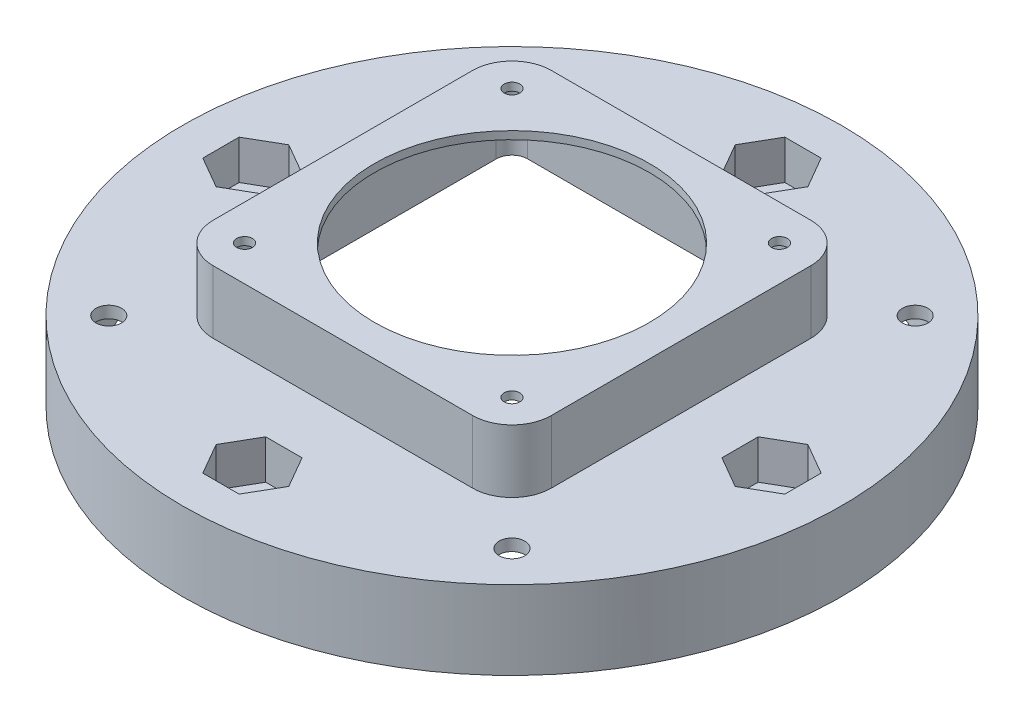
SolidWorks part; units mm, degrees
ref_plane "Front" through (0, 0, 0) normal (0, 0, 1) x (1, 0, 0)
ref_plane "Top" through (0, 0, 0) normal (0, 1, 0) x (1, 0, 0)
ref_plane "Right" through (0, 0, 0) normal (1, 0, 0) x (0, 0, -1)
sketch "Sketch1" plane through (0, 0, 0) normal (0, 1, 0) x (1, 0, 0)
  circle A0 centre (0, 0) radius 41.9
  dimension "D1" = 83.8
extrude "Top-Part" add sketch "Sketch1" along normal blind 15
sketch "Sketch2" plane through (0, 15, 0) normal (0, 1, 0) x (1, 0, 0)
  circle A0 centre (0, 0) radius 30
  dimension "D1" = 60
extrude "Cut-Extrude1" cut sketch "Sketch2" against normal blind 20
fillet "Fillet1" radius 1.5 1 edges at (0, 15, 41.9)
chamfer "Chamfer1" distance 2 angle 45 1 edges at (0, 15, 30)
sketch "Sketch8" plane through (0, 15, 0) normal (0, 1, 0) x (1, 0, 0)
  line L0 (0, 0) -> (0, 52.711) construction
  line L1 (25.0832, 22.5168) -> (28.0563, 23.5989)
  line L8 (0, 0) -> (-43.3951, 43.3951) construction
  line L9 (-25.6326, 25.6326) -> (-25.6326, 34.5059) construction
  line L10 (-22.5168, 25.0832) -> (-23.5989, 28.0563)
  line L11 (-23.5989, 28.0563) -> (-26.7147, 28.6057)
  line L12 (-26.7147, 28.6057) -> (-28.7485, 26.182)
  line L13 (-28.7485, 26.182) -> (-27.6663, 23.2089)
  line L14 (-27.6663, 23.2089) -> (-24.5505, 22.6595)
  line L15 (-24.5505, 22.6595) -> (-22.5168, 25.0832)
  line L16 (28.0563, 23.5989) -> (28.6057, 26.7147)
  line L17 (28.6057, 26.7147) -> (26.182, 28.7485)
  line L18 (26.182, 28.7485) -> (23.2089, 27.6663)
  line L19 (23.2089, 27.6663) -> (22.6595, 24.5505)
  line L20 (22.6595, 24.5505) -> (25.0832, 22.5168)
  line L21 (0, 0) -> (43.3951, 43.3951) construction
  line L23 (22.5168, -25.0832) -> (23.5989, -28.0563)
  line L24 (23.5989, -28.0563) -> (26.7147, -28.6057)
  line L25 (26.7147, -28.6057) -> (28.7485, -26.182)
  line L26 (28.7485, -26.182) -> (27.6663, -23.2089)
  line L27 (27.6663, -23.2089) -> (24.5505, -22.6595)
  line L28 (24.5505, -22.6595) -> (22.5168, -25.0832)
  line L29 (0, 0) -> (43.3951, -43.3951) construction
  line L31 (-25.0832, -22.5168) -> (-28.0563, -23.5989)
  line L32 (-28.0563, -23.5989) -> (-28.6057, -26.7147)
  line L33 (-28.6057, -26.7147) -> (-26.182, -28.7485)
  line L34 (-26.182, -28.7485) -> (-23.2089, -27.6663)
  line L35 (-23.2089, -27.6663) -> (-22.6595, -24.5505)
  line L36 (-22.6595, -24.5505) -> (-25.0832, -22.5168)
  line L37 (0, 0) -> (-43.3951, -43.3951) construction
  line L39 (-25.6326, 25.6326) -> (-27.9138, 12.6954) construction
  circle A0 centre (0, 0) radius 36.25 construction
  circle A1 centre (25.6326, 25.6326) radius 2.74 construction
  circle A2 centre (-25.6326, 25.6326) radius 2.74 construction
  circle A3 centre (25.6326, -25.6326) radius 2.74 construction
  circle A4 centre (-25.6326, -25.6326) radius 2.74 construction
  circle A5 centre (-25.6326, 25.6326) radius 1.625
  circle A6 centre (25.6326, 25.6326) radius 1.625
  circle A7 centre (25.6326, -25.6326) radius 1.625
  circle A8 centre (-25.6326, -25.6326) radius 1.625
  point P8 (25.6326, 25.6326)
  point P10 (28.331, 25.1568)
  point P18 (-25.6326, 25.6326)
  point P20 (-25.1568, 28.331)
  point P36 (25.6326, -25.6326)
  point P38 (25.1568, -28.331)
  point P50 (-25.6326, -25.6326)
  point P52 (-28.331, -25.1568)
  point P63 (0, 0)
  point P69 (-27.8231, 23.2366)
  dimension "D1" = 72.5
  dimension "D5" = 3.25
  dimension "D2" = 4
  dimension "D3" = 45
  dimension "D4" = 10
  dimension "D6" = 5.75
extrude "Cut-Extrude8" cut sketch "Sketch8<7>" against normal blind 3
sketch "Sketch8<7>" plane through (0, 15, 0) normal (0, 1, 0) x (1, 0, 0) same geometry as "Sketch8"
extrude "Cut-Extrude7" cut sketch "Sketch8" against normal through all contours A5 | A6 | A7 | A8
sketch "Sketch13" plane through (0, 0, 0) normal (0, -1, 0) x (1, 0, 0)
  line L0 (0, 0) -> (0, 66.0162) construction
  line L1 (-10, 35.5191) -> (-10, 40.6892)
  line L2 (10, 35.5191) -> (10, 40.6892)
  line L3 (-10, 40.6892) -> (10, 35.5191) construction
  line L4 (10, 40.6892) -> (-10, 35.5191) construction
  circle A0 centre (0, 0) radius 41.9 construction
  arc A1 (10, 40.6892) -> (-10, 40.6892) centre (0, 0) ccw
  arc A2 (10, 35.5191) -> (-10, 35.5191) centre (0, 0) ccw
  point P6 (0, 38.1042)
  point P10 (0, 36.9)
  point P12 (0, 41.9)
  dimension "D1" = 10
  dimension "D3" = 5
extrude "Cut-Extrude11" cut sketch "Sketch13" against normal through all
ref_plane "Plane2" through (0, 0, 41.9) normal (0, 0, 1) x (1, 0, 0)
ref_plane "Plane3" through (0, 0, 32.4) normal (0, 0, 1) x (1, 0, 0)
sketch "Sketch15" plane through (0, 0, 32.4) normal (0, 0, 1) x (1, 0, 0)
  line L0 (0, -23.0183) -> (0, 33.1182) construction
  circle A1 centre (0, 7.5) radius 1.625
  point P11 (0, 7.5)
  dimension "D3" = 3.25
  dimension "D1" = 7.5
extrude "Cut-Extrude14" cut sketch "Sketch15" against normal blind 10 and the other way blind 10
sketch "Sketch16" plane through (0, 0, 32.4) normal (0, 0, 1) x (1, 0, 0)
  line L0 (0, 0) -> (0, 26.985) construction
  line L2 (3.3775, 7.5) -> (1.6887, 10.425)
  line L3 (1.6887, 10.425) -> (-1.6887, 10.425)
  line L4 (-1.6887, 10.425) -> (-3.3775, 7.5)
  line L5 (-3.3775, 7.5) -> (-1.6887, 4.575)
  line L6 (-1.6887, 4.575) -> (1.6887, 4.575)
  line L7 (1.6887, 4.575) -> (3.3775, 7.5)
  circle A0 centre (0, 7.5) radius 2.925 construction
  point P4 (0, 4.575)
  point P13 (0, 10.425)
  dimension "D1" = 5.85
  dimension "D2" = 7.5
extrude "Cut-Extrude15" cut sketch "Sketch16" against normal blind 10
pattern_circular "CirPattern1" count 4 over 360 about axis through (0, 0, 0) along (0, 1, 0) of "Cut-Extrude14"
pattern_circular "CirPattern2" count 4 every 90 about axis through (0, 0, 0) along (0, 1, 0) of "Cut-Extrude15"
sketch "Sketch3" plane through (0, 0, 0) normal (0, -1, 0) x (1, 0, 0)
  circle A0 centre (0, 0) radius 41.9
  dimension "D1" = 83.8
extrude "Bottom-Part" add sketch "Sketch3" along normal blind 20 separate body
ref_plane "Plane1" through (0, -1.5, 0) normal (0, 1, 0) x (1, 0, 0)
sketch "Sketch6" plane through (0, -1.5, 0) normal (0, 1, 0) x (1, 0, 0)
  line L0 (0, 0) -> (-97.4577, 0) construction
  line L5 (-37.9, 0) -> (-41.9, 0) construction
  circle A0 centre (0, 0) radius 37.9
  circle A1 centre (0, 0) radius 41.9 construction
  circle A2 centre (0, 0) radius 41.9 construction
  point P6 (-37.9, 0)
  point P9 (-41.9, 0)
  dimension "D1" = 4
extrude "Cut-Extrude3" cut sketch "Sketch6" against normal through all
sketch "ｽｹｯﾁ1" plane through (0, 0, 0) normal (0, 1, 0) x (1, 0, 0)
  line L3 (21.5, -21.5) -> (-21.5, -21.5)
  line L4 (21.5, -21.5) -> (21.5, 21.5)
  line L5 (21.5, 21.5) -> (-21.5, 21.5)
  line L6 (-21.5, -21.5) -> (-21.5, 21.5)
  line L7 (21.5, -21.5) -> (-21.5, 21.5) construction
  line L8 (21.5, 21.5) -> (-21.5, -21.5) construction
  point P2 (0, 0)
  dimension "D1" = 43
extrude "ﾎﾞｽ - 押し出し1" add sketch "ｽｹｯﾁ1" along normal blind 8
fillet "ﾌｨﾚｯﾄ1" radius 5 4 edges at (21.5, 4, -21.5) (-21.5, 4, -21.5) (-21.5, 4, 21.5) (21.5, 4, 21.5)
sketch "Sketch7" plane through (0, -1.5, 0) normal (0, 1, 0) x (1, 0, 0)
  circle A0 centre (0, 0) radius 17.5
  circle A1 centre (17, -17) radius 1
  circle A2 centre (-17, -17) radius 1
  circle A3 centre (-17, 17) radius 1
  circle A4 centre (17, 17) radius 1
  dimension "D1" = 35
  dimension "D2" = 2
extrude "Cut-Extrude4" cut sketch "Sketch7" against normal through all and the other way through all
sketch "Sketch12" plane through (0, -1.5, 0) normal (0, -1, 0) x (1, 0, 0)
  line L1 (19.75, -19.75) -> (-19.75, -19.75)
  line L2 (19.75, -19.75) -> (19.75, 19.75)
  line L3 (19.75, 19.75) -> (-19.75, 19.75)
  line L4 (-19.75, -19.75) -> (-19.75, 19.75)
  line L5 (19.75, -19.75) -> (-19.75, 19.75) construction
  line L6 (19.75, 19.75) -> (-19.75, -19.75) construction
  point P0 (0, 0)
  dimension "D1" = 39.5
extrude "Cut-Extrude10" cut sketch "Sketch12" against normal blind 8.5
fillet "Fillet3" radius 2 4 edges at (-19.75, 2.75, -19.75) (-19.75, 2.75, 19.75) (19.75, 2.75, -19.75) (19.75, 2.75, 19.75)
sketch "Sketch17" plane through (0, -1.5, 0) normal (0, -1, 0) x (1, 0, 0)
  circle A0 centre (25.6326, -25.6326) radius 1.625 construction
  circle A1 centre (-25.6326, -25.6326) radius 1.625 construction
  circle A2 centre (25.6326, 25.6326) radius 1.625 construction
  circle A3 centre (-25.6326, 25.6326) radius 1.625 construction
  circle A4 centre (25.6326, -25.6326) radius 1.625
  circle A5 centre (-25.6326, -25.6326) radius 1.625
  circle A6 centre (25.6326, 25.6326) radius 1.625
  circle A7 centre (-25.6326, 25.6326) radius 1.625
extrude "Cut-Extrude16" cut sketch "Sketch17" against normal through all
sketch "Sketch18" plane through (0, -1.5, 0) normal (0, -1, 0) x (1, 0, 0)
  circle A0 centre (-25.6326, 25.6326) radius 3
  circle A1 centre (25.6326, 25.6326) radius 3
  circle A2 centre (25.6326, -25.6326) radius 3
  circle A3 centre (-25.6326, -25.6326) radius 3
  dimension "D1" = 6
extrude "Cut-Extrude17" cut sketch "Sketch18" along normal through all
sketch "Sketch19" plane through (0, -1.5, 0) normal (0, -1, 0) x (1, 0, 0)
  line L0 (-6, 33) -> (-6, 37.4221)
  line L1 (6, 33) -> (6, 37.4221)
  line L2 (33, 6) -> (37.4221, 6)
  line L3 (33, -6) -> (37.4221, -6)
  line L4 (6, -33) -> (6, -37.4221)
  line L5 (-6, -33) -> (-6, -37.4221)
  line L6 (-33, -6) -> (-37.4221, -6)
  line L7 (-33, 6) -> (-37.4221, 6)
  arc A0 (-6, 33) -> (6, 33) centre (0, 33) ccw
  arc A1 (24.9276, 28.5486) -> (-24.9276, 28.5486) centre (0, 0) ccw construction
  arc A2 (24.9276, 28.5486) -> (-24.9276, 28.5486) centre (0, 0) ccw construction
  arc A3 (6, 37.4221) -> (-6, 37.4221) centre (0, 0) ccw
  arc A4 (37.4221, -6) -> (37.4221, 6) centre (0, 0) ccw
  arc A5 (33, 6) -> (33, -6) centre (33, 0) ccw
  arc A6 (-6, -37.4221) -> (6, -37.4221) centre (0, 0) ccw
  arc A7 (6, -33) -> (-6, -33) centre (0, -33) ccw
  arc A8 (-37.4221, 6) -> (-37.4221, -6) centre (0, 0) ccw
  arc A9 (-33, -6) -> (-33, 6) centre (-33, 0) ccw
  circle A10 centre (0, 33) radius 2.75
  circle A11 centre (33, 0) radius 2.75
  circle A12 centre (0, -33) radius 2.75
  circle A13 centre (-33, 0) radius 2.75
  dimension "D1" = 12
  dimension "D4" = 4
  dimension "D2" = 33
  dimension "D3" = 4
extrude "Boss-Extrude1" add sketch "Sketch19" along normal up to surface (18.5 mm away) up to face at (0, -20, 0)
sketch "Sketch20" plane through (0, -20, 0) normal (0, -1, 0) x (1, 0, 0)
  line L1 (-43.8995, -46.5498) -> (43.8995, -46.5498)
  line L2 (-43.8995, -46.5498) -> (-43.8995, 46.5498)
  line L3 (-43.8995, 46.5498) -> (43.8995, 46.5498)
  line L4 (43.8995, -46.5498) -> (43.8995, 46.5498)
  line L5 (-43.8995, -46.5498) -> (43.8995, 46.5498) construction
  line L6 (-43.8995, 46.5498) -> (43.8995, -46.5498) construction
  point P0 (0, 0)
extrude "Cut-Extrude18" cut sketch "Sketch20" against normal blind 10
sketch "Sketch21" plane through (0, 15, 0) normal (0, 1, 0) x (1, 0, 0)
  line L1 (-10, -34.9) -> (10, -34.9)
  line L2 (-10, -34.9) -> (-10, -43.5518)
  line L3 (-10, -43.5518) -> (10, -43.5518)
  line L4 (10, -34.9) -> (10, -43.5518)
  dimension "D1" = 34.9
extrude "Cut-Extrude19" cut sketch "Sketch21" against normal up to surface (15 mm away) up to face at (-25.6326, 0, -27.2576)
sketch "Sketch22" plane through (0, 15, 0) normal (0, 1, 0) x (1, 0, 0)
  circle A0 centre (0, 0) radius 30
  circle A1 centre (0, 0) radius 41.9
extrude "Cut-Extrude20" cut sketch "Sketch22" against normal up to surface (15 mm away) up to face at (0, 0, -41.9)
sketch "Sketch23" plane through (0, -10, 0) normal (0, -1, 0) x (1, 0, 0)
  circle A0 centre (0, 33) radius 2.75
  circle A1 centre (-33, 0) radius 2.75
  circle A2 centre (0, -33) radius 2.75
  circle A3 centre (33, 0) radius 2.75
extrude "Cut-Extrude21" cut sketch "Sketch23" against normal through all
sketch "Sketch24" plane through (0, 0, 0) normal (0, 1, 0) x (1, 0, 0)
  line L0 (37, -2.3094) -> (37, 2.3094)
  line L1 (4.6188, 33) -> (2.3094, 37)
  line L2 (2.3094, 37) -> (-2.3094, 37)
  line L3 (-2.3094, 37) -> (-4.6188, 33)
  line L4 (-4.6188, 33) -> (-2.3094, 29)
  line L5 (-2.3094, 29) -> (2.3094, 29)
  line L6 (2.3094, 29) -> (4.6188, 33)
  line L7 (37, 2.3094) -> (33, 4.6188)
  line L8 (33, 4.6188) -> (29, 2.3094)
  line L9 (29, 2.3094) -> (29, -2.3094)
  line L10 (29, -2.3094) -> (33, -4.6188)
  line L11 (33, -4.6188) -> (37, -2.3094)
  line L12 (-2.3094, -37) -> (2.3094, -37)
  line L13 (2.3094, -37) -> (4.6188, -33)
  line L14 (4.6188, -33) -> (2.3094, -29)
  line L15 (2.3094, -29) -> (-2.3094, -29)
  line L16 (-2.3094, -29) -> (-4.6188, -33)
  line L17 (-4.6188, -33) -> (-2.3094, -37)
  line L18 (-37, 2.3094) -> (-37, -2.3094)
  line L19 (-37, -2.3094) -> (-33, -4.6188)
  line L20 (-33, -4.6188) -> (-29, -2.3094)
  line L21 (-29, -2.3094) -> (-29, 2.3094)
  line L22 (-29, 2.3094) -> (-33, 4.6188)
  line L23 (-33, 4.6188) -> (-37, 2.3094)
  circle A0 centre (0, 33) radius 4 construction
  dimension "D1" = 8
  dimension "D2" = 4
extrude "Cut-Extrude22" cut sketch "Sketch24" against normal blind 5
sketch "Sketch25" plane through (0, 0, 0) normal (0, 1, 0) x (1, 0, 0)
  line L0 (16.5, 21.5) -> (-16.5, 21.5) construction
  line L1 (16.5, 21.5) -> (-16.5, 21.5) construction
  circle A0 centre (-2, 22.5) radius 1
  circle A1 centre (2, 22.5) radius 1
  dimension "D1" = 2
  dimension "D2" = 2
  dimension "D3" = 1
  dimension "D4" = 1
  dimension "D5" = 2
  dimension "D6" = 2
extrude "Cut-Extrude23" cut sketch "Sketch25" against normal blind 10
